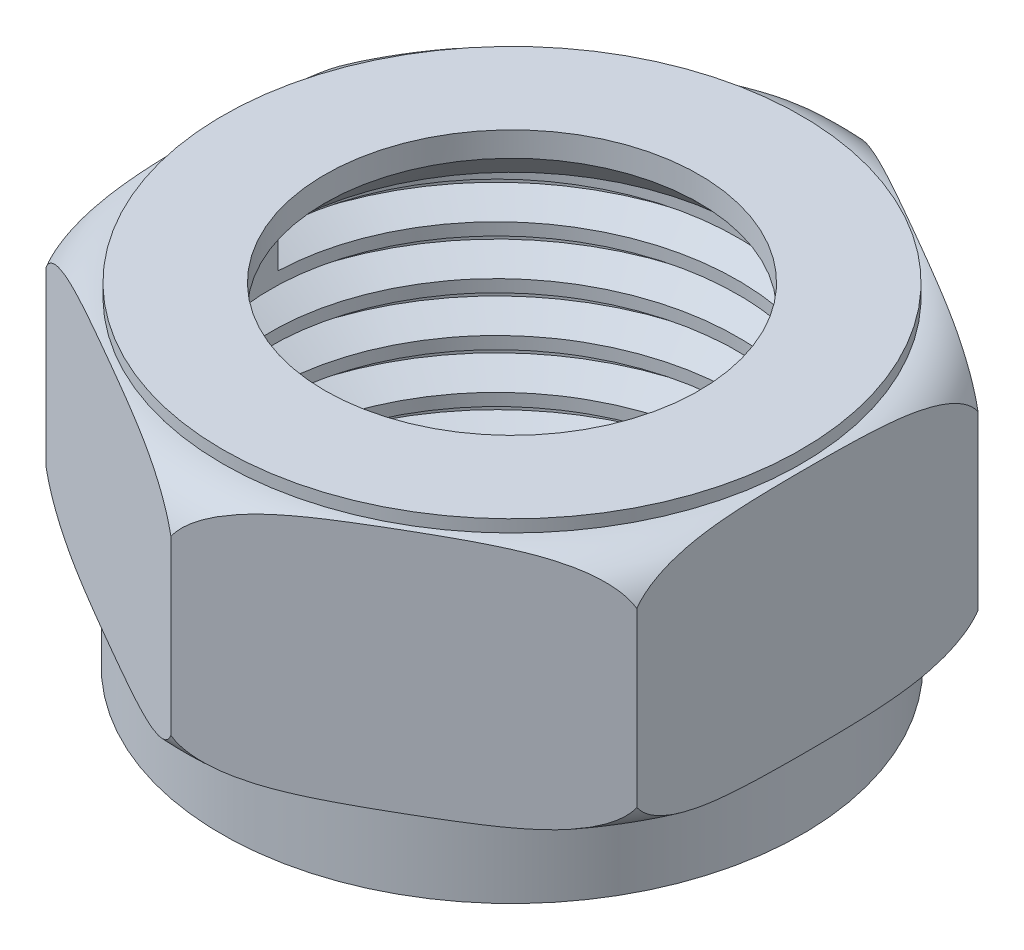
SolidWorks part; units mm, degrees
material "Brass"
ref_plane "Front" through (0, 0, 0) normal (0, 0, 1) x (1, 0, 0)
ref_plane "Top" through (0, 0, 0) normal (0, 1, 0) x (1, 0, 0)
ref_plane "Right" through (0, 0, 0) normal (1, 0, 0) x (0, 0, -1)
ref_axis "Axis1" through (0, 55, 0) along (0, -1, 0)
ref_axis "Axis2" through (88.99, 0, 0) along (-1, 0, 0)
ref_axis "Axis3" through (0, 0, 55) along (0, 0, -1)
sketch "Sketch1" plane through (0, 0, 0) normal (0, 1, 0) x (1, 0, 0)
  line L1 (12, 6.9282) -> (0, 13.8564)
  line L2 (0, 13.8564) -> (-12, 6.9282)
  line L3 (-12, 6.9282) -> (-12, -6.9282)
  line L4 (-12, -6.9282) -> (0, -13.8564)
  line L5 (0, -13.8564) -> (12, -6.9282)
  line L6 (12, -6.9282) -> (12, 6.9282)
  circle A0 centre (0, 0) radius 12 construction
  dimension "D1" = 24
extrude "Boss-Extrude1" add sketch "Sketch1" along normal mid plane 13.5
sketch "Sketch2" plane through (0, 6.75, 0) normal (0, 1, 0) x (1, 0, 0)
  line L6 (12, -6.9282) -> (12, 6.9282)
  line L7 (12, 6.9282) -> (0, 13.8564)
  line L8 (0, 13.8564) -> (-12, 6.9282)
  line L9 (-12, 6.9282) -> (-12, -6.9282)
  line L10 (-12, -6.9282) -> (0, -13.8564)
  line L11 (0, -13.8564) -> (12, -6.9282)
  line L12 (12, -6.9282) -> (12, 6.9282)
  line L13 (12, 6.9282) -> (0, 13.8564)
  line L14 (0, 13.8564) -> (-12, 6.9282)
  line L15 (-12, 6.9282) -> (-12, -6.9282)
  line L16 (-12, -6.9282) -> (0, -13.8564)
  line L17 (0, -13.8564) -> (12, -6.9282)
  circle A0 centre (0, 0) radius 11.75
  dimension "D1" = 23.5
  dimension "D2" = 0
extrude "Cut-Extrude1" cut sketch "Sketch2" against normal blind 0.5
sketch "Sketch3" plane through (0, -6.75, 0) normal (0, -1, 0) x (1, 0, 0)
  line L6 (12, -6.9282) -> (12, 6.9282)
  line L7 (12, 6.9282) -> (0, 13.8564)
  line L8 (0, 13.8564) -> (-12, 6.9282)
  line L9 (-12, 6.9282) -> (-12, -6.9282)
  line L10 (-12, -6.9282) -> (0, -13.8564)
  line L11 (0, -13.8564) -> (12, -6.9282)
  line L12 (12, -6.9282) -> (12, 6.9282)
  line L13 (12, 6.9282) -> (0, 13.8564)
  line L14 (0, 13.8564) -> (-12, 6.9282)
  line L15 (-12, 6.9282) -> (-12, -6.9282)
  line L16 (-12, -6.9282) -> (0, -13.8564)
  line L17 (0, -13.8564) -> (12, -6.9282)
  circle A0 centre (0, 0) radius 11.8
  dimension "D1" = 23.6
  dimension "D2" = 0
extrude "Cut-Extrude2" cut sketch "Sketch3" against normal blind 3
ref_plane "Plane2" through (0, 1.25, 0) normal (0, 1, 0) x (1, 0, 0)
sketch "Sketch8" plane through (0, 0, 0) normal (1, 0, 0) x (0, 0, -1)
  line L0 (0, 6.75) -> (0, -6.75) construction
  line L1 (11.75, 6.75) -> (-11.75, 6.75) construction
  line L2 (-11.8, -6.75) -> (11.8, -6.75) construction
  line L3 (-13.8564, 6.25) -> (-13.8564, -3.75) construction
  line L4 (-13.8564, 6.25) -> (-6.9282, 6.25) construction
  line L5 (-11.75, 6.25) -> (-13.8564, 6.25)
  line L6 (-13.8564, 6.25) -> (-13.8564, 4.75)
  arc A0 (-11.75, 6.25) -> (-13.8564, 4.75) centre (-11.75, 4.021) ccw
  dimension "D1" = 1.5
revolve "Cut-Revolve2" cut sketch "Sketch8" angle 360 about L0
mirror "Mirror1" about plane through (0, 1.25, 0) normal (0, 1, 0) of "Cut-Revolve2"
sketch "Sketch5" plane through (0, 0, 0) normal (1, 0, 0) x (0, 0, -1)
  line L0 (0, 6.75) -> (0, -6.75) construction
  line L1 (11.75, 6.75) -> (-11.75, 6.75) construction
  line L2 (-11.8, -6.75) -> (11.8, -6.75) construction
  line L3 (-7.6, 6.75) -> (-7.6, 5.75)
  line L4 (-7.6, 5.75) -> (-9.5, 3.9152)
  line L5 (-9.5, 3.9152) -> (-9.5, -6.75)
  line L6 (-9.5, -6.75) -> (0, -6.75)
  line L7 (-7.6, 6.75) -> (0, 6.75)
  line L10 (0, 6.75) -> (0, -6.75)
  dimension "D1" = 19
  dimension "D2" = 1
  dimension "D3" = 44
  dimension "D4" = 15.2
revolve "Cut-Revolve1" cut sketch "Sketch5" angle 360 about L0
thread "Thread1" pitch 2 method cut profile "Thread Profile1" start angle 0, offset 0, length 20, pitch 2, diameter 19
ref_plane "Plane1" through (-9.5, 3.9152, 0) normal (0, 0, 1) x (-1, 0, 0)
sketch "Thread Profile1" plane through (-9.5, 3.9152, 0) normal (0, 0, 1) x (-1, 0, 0)
  line L0 (0, 0) -> (0, 2) construction
  line L1 (0, 0) -> (1.0825, 0.625)
  line L2 (1.0825, 0.625) -> (1.0825, 0.875)
  line L3 (1.0825, 0.875) -> (0, 1.5)
  line L4 (1.0825, 0.75) -> (0, 0.75) construction
  line L11 (0, 0) -> (0, 1.5)
  point P2 (0, 0)
  dimension "Pitch" = 2
  dimension "Profile_Angle" = 60
  dimension "Profile_Land" = 0.25
  dimension "Profile_Height" = 1.0825
